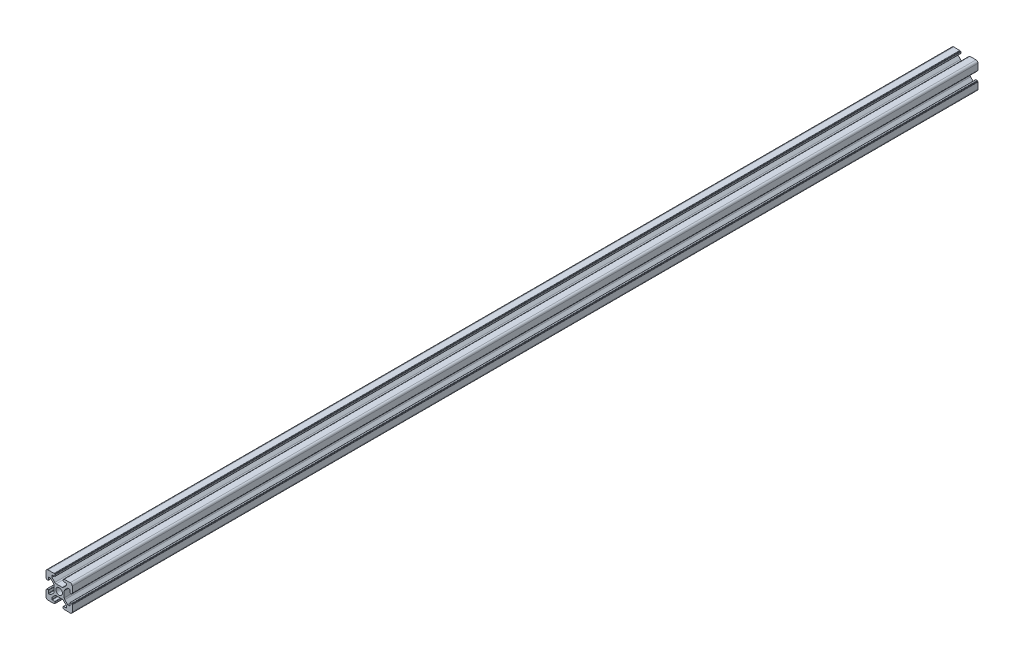
SolidWorks part; units mm, degrees
material "1060 Alloy"
ref_plane "Front Plane" through (0, 0, 0) normal (0, 0, 1) x (1, 0, 0)
ref_plane "Top Plane" through (0, 0, 0) normal (0, 1, 0) x (1, 0, 0)
ref_plane "Right Plane" through (0, 0, 0) normal (1, 0, 0) x (0, 0, -1)
sketch "Sketch1" plane through (0, 0, 0) normal (0, 0, 1) x (1, 0, 0)
  line L0 (3.8995, 3.9005) -> (10.4604, 10.4604) construction
  line L2 (-3.9002, 2.2177) -> (-3.9002, -2.2208)
  line L5 (-3.9005, 3.899) -> (3.9001, -3.8986) construction
  line L6 (-3.9, -3.901) -> (3.8995, 3.9005) construction
  line L7 (-0.0002, 10) -> (-0.0002, -9.9996) construction
  line L8 (-0.0002, -9.9996) -> (-0.0002, 10) construction
  line L9 (5.5006, 6.5619) -> (3.2793, 4.3405)
  line L14 (-10.0002, 9.9996) -> (9.9994, -10) construction
  line L15 (-9.9999, -10.0001) -> (9.9998, 10) construction
  line L16 (6.5613, 5.5012) -> (4.3401, 3.28)
  line L17 (-5.5002, 6.5603) -> (-3.279, 4.3391)
  line L18 (-6.5609, 5.4996) -> (-4.3395, 3.2783)
  line L19 (7.9206, 5.5012) -> (6.5613, 5.5012)
  line L20 (8.2006, 3.3812) -> (8.2006, 5.2212)
  line L21 (9.4206, 3.1012) -> (8.4806, 3.1012)
  line L22 (9.7006, 3.6012) -> (9.7006, 3.3812)
  line L23 (-8.5002, 9.9996) -> (-3.8802, 9.9996)
  line L24 (-3.6002, 9.7196) -> (-3.6002, 9.6996)
  line L25 (-3.6002, 9.6996) -> (-3.3802, 9.6996)
  line L26 (-3.1002, 9.4196) -> (-3.1002, 8.4796)
  line L27 (-3.3802, 8.1996) -> (-5.2202, 8.1996)
  line L28 (-5.5002, 7.9196) -> (-5.5002, 6.5603)
  line L29 (-7.9202, 5.4996) -> (-6.5609, 5.4996)
  line L30 (-8.2002, 3.3796) -> (-8.2002, 5.2196)
  line L31 (-9.4202, 3.0996) -> (-8.4802, 3.0996)
  line L32 (-9.7202, 3.5996) -> (-9.7002, 3.5996)
  line L33 (-9.7002, 3.5996) -> (-9.7002, 3.3796)
  line L34 (-10.0002, 8.4996) -> (-10.0002, 3.8796)
  line L35 (10.0006, 8.5012) -> (10.0006, 3.8812)
  line L36 (8.5006, 10.0012) -> (3.8806, 10.0012)
  line L37 (3.6006, 9.7012) -> (3.3806, 9.7012)
  line L38 (3.1006, 9.4212) -> (3.1006, 8.4812)
  line L39 (3.3806, 8.2012) -> (5.2206, 8.2012)
  line L40 (5.5006, 7.9212) -> (5.5006, 6.5619)
  line L41 (6.5629, -5.4996) -> (4.3415, -3.2783)
  line L42 (5.5022, -6.5603) -> (3.281, -4.3391)
  line L43 (5.5022, -7.9196) -> (5.5022, -6.5603)
  line L44 (3.3822, -8.1996) -> (5.2222, -8.1996)
  line L45 (3.1022, -9.4196) -> (3.1022, -8.4796)
  line L46 (3.6022, -9.6996) -> (3.3822, -9.6996)
  line L47 (8.5022, -9.9996) -> (3.8822, -9.9996)
  line L48 (10.0022, -8.4996) -> (10.0022, -3.8796)
  line L49 (9.7022, -3.5996) -> (9.7022, -3.3796)
  line L50 (9.4222, -3.0996) -> (8.4822, -3.0996)
  line L51 (8.2022, -3.3796) -> (8.2022, -5.2196)
  line L52 (7.9222, -5.4996) -> (6.5629, -5.4996)
  line L53 (-5.4986, -6.5619) -> (-3.2773, -4.3405)
  line L54 (-6.5593, -5.5012) -> (-4.3395, -3.2814)
  line L55 (-7.9186, -5.5012) -> (-6.5593, -5.5012)
  line L56 (-8.1986, -3.3812) -> (-8.1986, -5.2212)
  line L57 (-9.4186, -3.1012) -> (-8.4786, -3.1012)
  line L58 (-9.6986, -3.6012) -> (-9.6986, -3.3812)
  line L59 (-9.9986, -8.5012) -> (-9.9986, -3.8812)
  line L60 (-8.4986, -10.0012) -> (-3.8786, -10.0012)
  line L61 (-3.5986, -9.7012) -> (-3.3786, -9.7012)
  line L62 (-3.0986, -9.4212) -> (-3.0986, -8.4812)
  line L63 (-3.3786, -8.2012) -> (-5.2186, -8.2012)
  line L64 (-5.4986, -7.9212) -> (-5.4986, -6.5619)
  line L65 (-2.233, 3.8998) -> (2.2187, 3.9012)
  line L66 (3.9008, 2.234) -> (3.9022, -2.2177)
  line L67 (2.235, -3.8998) -> (-2.2167, -3.9012)
  line L68 (3.6006, 9.7212) -> (3.6006, 9.6996)
  line L69 (9.7006, 3.6012) -> (9.7206, 3.6012)
  line L70 (-9.6986, -3.6012) -> (-9.7186, -3.6012)
  line L71 (-3.5986, -9.7012) -> (-3.5986, -9.7212)
  line L72 (3.6022, -9.6996) -> (3.6022, -9.7196)
  line L73 (9.7222, -3.5996) -> (9.7022, -3.5996)
  arc A0 (-3.6002, 9.7196) -> (-3.8802, 9.9996) centre (-3.8802, 9.7196) ccw
  arc A1 (-3.3802, 9.6996) -> (-3.1002, 9.4196) centre (-3.3802, 9.4196) cw
  arc A2 (-3.1002, 8.4796) -> (-3.3802, 8.1996) centre (-3.3802, 8.4796) cw
  arc A3 (-10.0002, 8.4996) -> (-8.5002, 9.9996) centre (-8.5002, 8.4996) cw
  arc A4 (-8.2002, 3.3796) -> (-8.4802, 3.0996) centre (-8.4802, 3.3796) cw
  arc A5 (-9.4202, 3.0996) -> (-9.7002, 3.3796) centre (-9.4202, 3.3796) cw
  arc A6 (-9.7202, 3.5996) -> (-10.0002, 3.8796) centre (-9.7202, 3.8796) cw
  arc A7 (-3.279, 4.3391) -> (-2.233, 3.8998) centre (-2.2183, 5.3997) ccw
  arc A8 (-4.3395, 3.2783) -> (-3.9002, 2.2177) centre (-5.4002, 2.2177) cw
  arc A9 (-7.9202, 5.4996) -> (-8.2002, 5.2196) centre (-7.9202, 5.2196) ccw
  arc A10 (-5.2202, 8.1996) -> (-5.5002, 7.9196) centre (-5.2202, 7.9196) ccw
  arc A12 (-4.3395, -3.2814) -> (-3.9002, -2.2208) centre (-5.4002, -2.2208) ccw
  arc A13 (8.2006, 5.2212) -> (7.9206, 5.5012) centre (7.9206, 5.2212) ccw
  arc A14 (8.4806, 3.1012) -> (8.2006, 3.3812) centre (8.4806, 3.3812) cw
  arc A15 (9.7006, 3.3812) -> (9.4206, 3.1012) centre (9.4206, 3.3812) cw
  arc A16 (9.7206, 3.6012) -> (10.0006, 3.8812) centre (9.7206, 3.8812) ccw
  arc A17 (8.5006, 10.0012) -> (10.0006, 8.5012) centre (8.5006, 8.5012) cw
  arc A18 (3.6006, 9.7212) -> (3.8806, 10.0012) centre (3.8806, 9.7212) cw
  arc A19 (3.1006, 9.4212) -> (3.3806, 9.7012) centre (3.3806, 9.4212) cw
  arc A20 (3.3806, 8.2012) -> (3.1006, 8.4812) centre (3.3806, 8.4812) cw
  arc A21 (5.5006, 7.9212) -> (5.2206, 8.2012) centre (5.2206, 7.9212) ccw
  arc A22 (3.2793, 4.3405) -> (2.2187, 3.9012) centre (2.2187, 5.4012) cw
  arc A23 (4.3401, 3.28) -> (3.9008, 2.234) centre (5.4007, 2.2193) ccw
  arc A25 (5.2222, -8.1996) -> (5.5022, -7.9196) centre (5.2222, -7.9196) ccw
  arc A26 (3.1022, -8.4796) -> (3.3822, -8.1996) centre (3.3822, -8.4796) cw
  arc A27 (3.3822, -9.6996) -> (3.1022, -9.4196) centre (3.3822, -9.4196) cw
  arc A28 (3.6022, -9.7196) -> (3.8822, -9.9996) centre (3.8822, -9.7196) ccw
  arc A29 (10.0022, -8.4996) -> (8.5022, -9.9996) centre (8.5022, -8.4996) cw
  arc A30 (9.7222, -3.5996) -> (10.0022, -3.8796) centre (9.7222, -3.8796) cw
  arc A31 (9.4222, -3.0996) -> (9.7022, -3.3796) centre (9.4222, -3.3796) cw
  arc A32 (8.2022, -3.3796) -> (8.4822, -3.0996) centre (8.4822, -3.3796) cw
  arc A33 (7.9222, -5.4996) -> (8.2022, -5.2196) centre (7.9222, -5.2196) ccw
  arc A34 (4.3415, -3.2783) -> (3.9022, -2.2177) centre (5.4022, -2.2177) cw
  arc A35 (3.281, -4.3391) -> (2.235, -3.8998) centre (2.2203, -5.3997) ccw
  circle A36 centre (0.001, -0.001) radius 2.5 construction
  arc A37 (-8.1986, -5.2212) -> (-7.9186, -5.5012) centre (-7.9186, -5.2212) ccw
  arc A38 (-8.4786, -3.1012) -> (-8.1986, -3.3812) centre (-8.4786, -3.3812) cw
  arc A39 (-9.6986, -3.3812) -> (-9.4186, -3.1012) centre (-9.4186, -3.3812) cw
  arc A40 (-9.7186, -3.6012) -> (-9.9986, -3.8812) centre (-9.7186, -3.8812) ccw
  arc A41 (-8.4986, -10.0012) -> (-9.9986, -8.5012) centre (-8.4986, -8.5012) cw
  arc A42 (-3.5986, -9.7212) -> (-3.8786, -10.0012) centre (-3.8786, -9.7212) cw
  arc A43 (-3.0986, -9.4212) -> (-3.3786, -9.7012) centre (-3.3786, -9.4212) cw
  arc A44 (-3.3786, -8.2012) -> (-3.0986, -8.4812) centre (-3.3786, -8.4812) cw
  arc A45 (-5.4986, -7.9212) -> (-5.2186, -8.2012) centre (-5.2186, -7.9212) ccw
  arc A46 (-3.2773, -4.3405) -> (-2.2167, -3.9012) centre (-2.2167, -5.4012) cw
  arc A48 (-4.3381, -3.28) -> (-3.8988, -2.234) centre (-5.3987, -2.2193) ccw [skipped]
  point P0 (0, 0)
  point P9 (-0.0002, 0.0002)
  point P12 (-0.0003, -0.0003)
  point P43 (-3.6002, 9.9996)
  point P46 (-3.1002, 9.6996)
  point P49 (-3.1002, 8.1996)
  point P55 (-8.2002, 3.0996)
  point P58 (-9.7002, 3.0996)
  point P61 (-10.0002, 3.5996)
  point P64 (-2.8395, 3.8996)
  point P67 (-3.9002, 2.839)
  point P70 (-8.2002, 5.4996)
  point P73 (-5.5002, 8.1996)
  point P184 (0.001, 0)
  dimension "D14" = 0.28
  dimension "D15" = 0.28
  dimension "D16" = 0.28
  dimension "D17" = 1.5
  dimension "D18" = 0.28
  dimension "D19" = 1.5
  dimension "D20" = 1.5
  dimension "D21" = 0.28
  dimension "D23" = 5
  dimension "D27" = 1.5
  dimension "D1" = 7.8
  dimension "D2" = 7.8
  dimension "D3" = 3.1
  dimension "D4" = 3.6
  dimension "D5" = 20
  dimension "D6" = 20
  dimension "D7" = 0.75
  dimension "D8" = 1.8
  dimension "D9" = 5.5
  dimension "D10" = 6.4
  dimension "D11" = 6.4
  dimension "D12" = 3.7627
  dimension "D13" = 0.3
  dimension "D24" = 4.62
  dimension "D25" = 3.9005
  dimension "D26" = 7.801
  dimension "D22" = 4
extrude "Boss-Extrude1" add sketch "Sketch1" along normal blind 690 contours L53 A46 L67 A35 L42 L43 A25 L44 A26 L45 A27 L46 L72 A28 L47 A29 L48 A30 L73 L49 A31 L50 A32 L51 A33 L52 L41 A34 L66 A23 L16 L19 A13 L20 A14 L21 A15 L22 L69 A16 L35 A17 L36 A18 L68 L37 A19 L38 A20 region at (0.0009, 0, 0)
sketch3d "3DSketch2"
  circle A0 centre (0, 0, 0) radius 2.5
  point P2 (0, 0, 2.5)
extrude "Cut-Extrude1" cut sketch "3DSketch2" along direction (0, 0, 1) on the side of the normal through all contours A0
